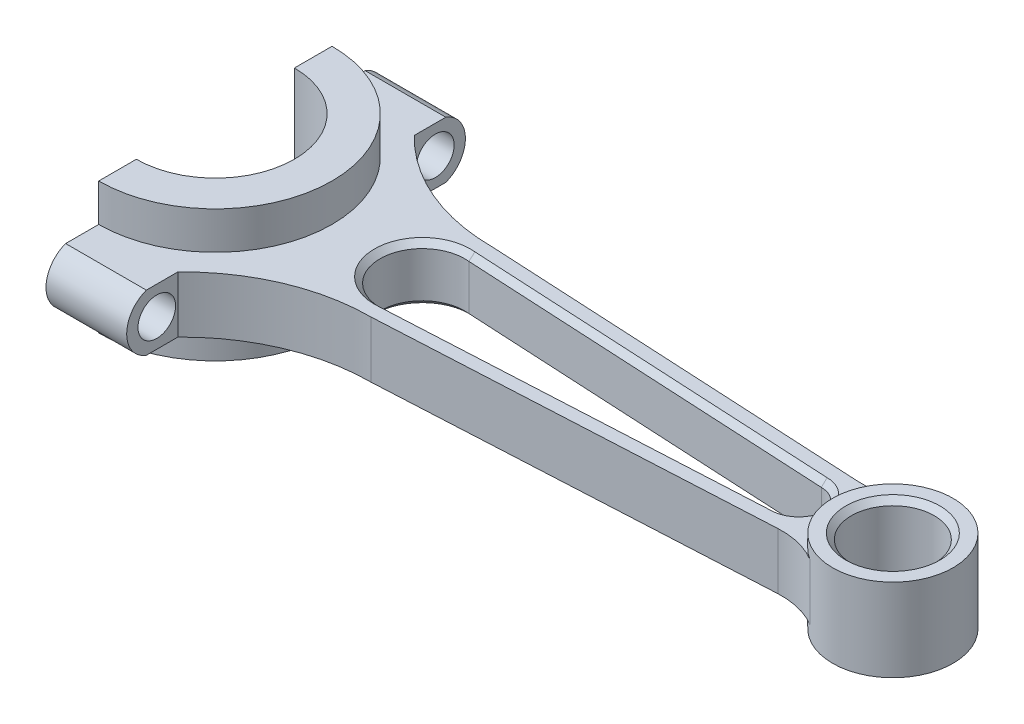
SolidWorks part; units mm, degrees
ref_plane "Front Plane" through (0, 0, 0) normal (0, 0, 1) x (1, 0, 0)
ref_plane "Top Plane" through (0, 0, 0) normal (0, 1, 0) x (1, 0, 0)
ref_plane "Right Plane" through (0, 0, 0) normal (1, 0, 0) x (0, 0, -1)
sketch "Sketch1" plane through (0, 0, 0) normal (0, 1, 0) x (1, 0, 0)
  line L0 (194.2047, 0) -> (2137.9595, 0) construction
  line L1 (-1646.6405, 533.4) -> (-1646.6405, 1143)
  line L2 (-1646.6405, 1143) -> (-1102.1786, 1143)
  line L3 (-1102.1786, 1143) -> (-1102.1786, 798.1009)
  line L4 (-187.7786, 409.448) -> (2615.1545, 262.5525)
  line L5 (-249.6405, 285.5158) -> (2290.3595, 152.4)
  line L6 (-249.6405, -285.5158) -> (2290.3595, -152.4)
  line L7 (-1646.6405, -533.4) -> (-1646.6405, -1143)
  line L8 (-1646.6405, -1143) -> (-1102.1786, -1143)
  line L9 (-1102.1786, -1143) -> (-1102.1786, -798.1009)
  line L10 (-187.7786, -409.448) -> (2615.1545, -262.5525)
  line L11 (2442.7595, 0) -> (2925.3595, 0) construction
  circle A0 centre (2925.3595, 0) radius 406.4
  circle A1 centre (2925.3595, 0) radius 279.4
  arc A2 (-1646.6405, -533.4) -> (-1646.6405, 533.4) centre (-1646.6405, 0) ccw
  arc A3 (-1646.6405, -787.4) -> (-1646.6405, 787.4) centre (-1646.6405, 0) ccw
  arc A4 (-1102.1786, 798.1009) -> (-187.7786, 409.448) centre (-187.7786, 1679.448) ccw
  arc A5 (-219.796, 283.9517) -> (-219.796, -283.9517) centre (-249.6405, 0) ccw
  arc A6 (2290.3595, -152.4) -> (2290.3595, 152.4) centre (2290.3595, 0) ccw
  arc A7 (-1102.1786, -798.1009) -> (-187.7786, -409.448) centre (-187.7786, -1679.448) cw
  dimension "D2" = 558.8
  dimension "D3" = 812.8
  dimension "D4" = 787.4
  dimension "D5" = 533.4
  dimension "D6" = 2540
  dimension "D9" = 304.8
  dimension "D12" = 3
  dimension "D1" = 4572
  dimension "D7" = 1679.448
  dimension "D8" = 914.4
  dimension "D10" = 2540
  dimension "D11" = 3175
  dimension "D13" = 1143
  dimension "D14" = 127
extrude "Boss-Extrude4" add sketch "Sketch1" along normal mid plane 889 contours L7 A3 L1 A2 region at (-1629.0337, 0, -660.4)
extrude "Boss-Extrude5" add sketch "Sketch1<6>" along normal mid plane 558.8 separate body contours A0 A1 region at (3061.215, 0, -370.8011)
sketch "Sketch1<6>" plane through (0, 0, 0) normal (0, 1, 0) x (1, 0, 0) same geometry as "Sketch1"
extrude "Boss-Extrude6" add sketch "Sketch1<7>" along normal mid plane 381 contours L9 A7 L10 A0 L4 A4 L3 L2 L1 A3 L7 L8 A6 L6 A5 L5 region at (-1598.2787, 0, -965.2)
sketch "Sketch1<7>" plane through (0, 0, 0) normal (0, 1, 0) x (1, 0, 0) same geometry as "Sketch1"
sketch "Sketch2" plane through (-1646.6405, 0, 0) normal (-1, 0, 0) x (0, 0, 1)
  line L0 (-939.8, 0) -> (-736.6, 0) construction
  line L2 (1143, 190.5) -> (1143, -190.5) construction
  line L3 (787.4, 190.5) -> (1143, 190.5) construction
  line L4 (-787.4, -190.5) -> (-1143, -190.5) construction
  line L5 (-1143, 190.5) -> (-1143, -190.5) construction
  line L6 (-787.4, 190.5) -> (-1143, 190.5) construction
  line L8 (1143, 190.5) -> (1143, -190.5)
  line L9 (1010.5106, 190.5) -> (1143, 190.5)
  line L10 (-1010.5106, -190.5) -> (-1143, -190.5)
  line L11 (-1143, 190.5) -> (-1143, -190.5)
  line L12 (-1010.5106, 190.5) -> (-1143, 190.5)
  line L13 (812.8, 0) -> (939.8, 0) construction
  line L14 (1010.5106, -190.5) -> (1143, -190.5)
  arc A0 (-1010.5106, 190.5) -> (-1010.5106, -190.5) centre (-939.8, 0) ccw
  circle A1 centre (-939.8, 0) radius 127
  arc A2 (1010.5106, -190.5) -> (1010.5106, 190.5) centre (939.8, 0) ccw
  circle A3 centre (939.8, 0) radius 127
  line M9 (-787.4, 190.5) -> (-1143, 190.5)
  line M10 (-1143, 190.5) -> (-1143, -190.5)
  line M11 (-1143, -190.5) -> (-787.4, -190.5)
  dimension "D2" = 406.4
  dimension "D3" = 254
  dimension "D1" = 1879.6
extrude "Cut-Extrude1" cut sketch "Sketch2" against normal up to surface (544.4619 mm away) contours A1 | A0 M9 M10 | A0 L11 M11 | A3 | A2 L14 L8 | A2 L8 L9 region at (-1646.6405, -146.4822, 1107.2038) region at (-1646.6405, 146.4822, 1107.2038) region at (-1646.6405, 146.4822, -1107.2038) region at (-1646.6405, -146.4822, -1107.2038) region at (-1646.6405, 0, -939.8) region at (-1646.6405, 0, 939.8) up to face at (-1102.1786, 0, -970.5505)
chamfer "Chamfer1" distance 38.1 angle 45 10 edges at (2925.3595, -279.4, 279.4) (1035.2817, -190.5, 218.1758) (2442.7595, -190.5, 0) (1035.2817, -190.5, -218.1758) (-535.1563, -190.5, 0) (2925.3595, 279.4, 279.4) (2442.7595, 190.5, 0) (1035.2817, 190.5, 218.1758) (1035.2817, 190.5, -218.1758) (-535.1563, 190.5, 0)
fillet "Fillet1" radius 508 2 edges at (2615.1545, 0, -262.5525) (2615.1545, 0, 262.5525)
